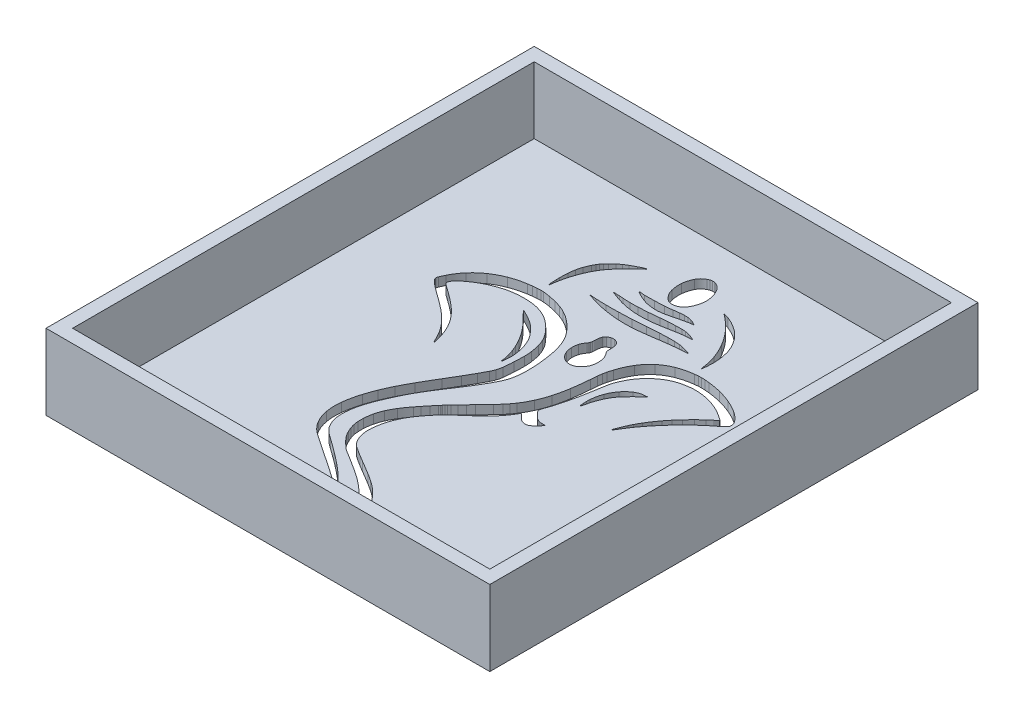
SolidWorks part; units mm, degrees
ref_plane "Front Plane" through (0, 0, 0) normal (0, 0, 1) x (1, 0, 0)
ref_plane "Top Plane" through (0, 0, 0) normal (0, 1, 0) x (1, 0, 0)
ref_plane "Right Plane" through (0, 0, 0) normal (1, 0, 0) x (0, 0, -1)
sketch "Sketch1" plane through (0, 0, 0) normal (0, 1, 0) x (1, 0, 0)
  line L1 (-50, 55) -> (50, 55)
  line L2 (-50, 55) -> (-50, -55)
  line L3 (-50, -55) -> (50, -55)
  line L4 (50, 55) -> (50, -55)
  line L5 (-50, 55) -> (50, -55) construction
  line L6 (-50, -55) -> (50, 55) construction
  point P0 (0, 0)
  dimension "D1" = 110
  dimension "D2" = 100
extrude "Boss-Extrude1" add sketch "Sketch1" along normal blind 2
sketch "Sketch2" plane through (0, 2, 0) normal (0, 1, 0) x (1, 0, 0)
  line L11 (50, 55) -> (-50, 55) construction
  line L12 (50, -55) -> (50, 55) construction
  line L13 (-50, -55) -> (50, -55) construction
  line L14 (-50, 55) -> (-50, -55) construction
  line L15 (47, 52) -> (-47, 52)
  line L16 (47, -52) -> (47, 52)
  line L17 (-47, -52) -> (47, -52)
  line L18 (-47, 52) -> (-47, -52)
  line L19 (47, 52) -> (-47, 52)
  line L20 (47, -52) -> (47, 52)
  line L21 (-47, -52) -> (47, -52)
  line L22 (-47, 52) -> (-47, -52)
  line L23 (50, 55) -> (-50, 55)
  line L24 (50, -55) -> (50, 55)
  line L25 (-50, -55) -> (50, -55)
  line L26 (-50, 55) -> (-50, -55)
  dimension "D1" = 3
extrude "Boss-Extrude2" add sketch "Sketch2" along normal blind 15
sketch "Sketch4" plane through (0, 0, 0) normal (0, -1, 0) x (1, 0, 0)
  line L0 (9.4741, -38.4821) -> (9.1865, -38.7106)
  line L1 (8.9359, -38.9105) -> (8.721, -39.0824)
  line L2 (6.9419, -33.8902) -> (7.3474, -33.6335)
  line L3 (7.3474, -33.6335) -> (6.6825, -33.5473)
  line L4 (6.9435, -30.2628) -> (6.2805, -30.1435)
  line L5 (6.2805, -30.1435) -> (5.4513, -29.9942)
  line L6 (5.4513, -29.9942) -> (4.5988, -29.8406)
  line L7 (4.5988, -29.8406) -> (3.8574, -29.707)
  line L8 (-8.9808, -27.3617) -> (-10.277, -27.7919)
  line L9 (-10.277, -27.7919) -> (-8.7339, -27.7062)
  line L10 (9.5003, 2.7221) -> (10.1461, 2.7221)
  line L11 (10.1461, 2.7221) -> (9.9335, 3.0852)
  line L12 (-5.4816, 10.5411) -> (-5.2835, 10.3261)
  line L13 (15.4299, -14.3103) -> (16.14, -14.3779)
  line L14 (16.14, -14.3779) -> (14.7062, -12.9744)
  arc A0 (1.7289, -44.1609) -> (2.2683, -43.8703) centre (0.2772, -40.8206) ccw
  arc A1 (2.2683, -43.8703) -> (2.7079, -43.5117) centre (0.8011, -41.623) ccw
  arc A2 (2.7079, -43.5117) -> (3.0821, -43.05) centre (0.582, -41.4061) ccw
  arc A3 (3.0821, -43.05) -> (3.426, -42.4476) centre (-1.521, -40.0232) ccw
  arc A4 (3.426, -42.4476) -> (3.7762, -41.5765) centre (-2.3242, -39.6296) ccw
  arc A5 (3.7762, -41.5765) -> (3.9968, -40.6604) centre (-2.4134, -39.6011) ccw
  arc A6 (3.9968, -40.6604) -> (4.0782, -39.7497) centre (-2.0474, -39.6616) ccw
  arc A7 (4.0782, -39.7497) -> (4.013, -38.895) centre (-0.6645, -39.6815) ccw
  arc A8 (4.013, -38.895) -> (3.5881, -37.3522) centre (-3.726, -40.1963) ccw
  arc A9 (3.5881, -37.3522) -> (2.895, -36.1872) centre (-0.2386, -38.8402) ccw
  arc A10 (2.895, -36.1872) -> (1.9771, -35.4661) centre (0.6794, -38.063) ccw
  arc A11 (1.9771, -35.4661) -> (0.8935, -35.2105) centre (0.8935, -37.6345) ccw
  arc A12 (0.8935, -35.2105) -> (0.3834, -35.2531) centre (0.8935, -38.2859) ccw
  arc A13 (0.3834, -35.2531) -> (-0.0297, -35.3822) centre (0.6475, -36.8233) ccw
  arc A14 (-0.0297, -35.3822) -> (-0.4186, -35.6279) centre (0.7597, -37.0622) ccw
  arc A15 (-0.4186, -35.6279) -> (-0.8579, -36.0335) centre (2.8687, -39.6292) ccw
  arc A16 (-0.8579, -36.0335) -> (-1.9288, -37.9241) centre (2.2762, -39.0575) ccw
  arc A17 (-1.9288, -37.9241) -> (-2.1348, -40.3651) centre (4.7098, -39.7134) ccw
  arc A18 (-2.1348, -40.3651) -> (-1.4793, -42.6246) centre (4.1492, -39.7668) ccw
  arc A19 (-1.4793, -42.6246) -> (-0.0989, -44.0059) centre (1.3285, -41.199) ccw
  arc A20 (-0.0989, -44.0059) -> (0.4205, -44.2275) centre (1.8111, -40.2501) ccw
  arc A21 (0.4205, -44.2275) -> (0.8661, -44.3227) centre (1.0195, -42.5143) ccw
  arc A22 (0.8661, -44.3227) -> (1.2871, -44.2992) centre (0.9933, -42.8237) ccw
  arc A23 (1.2871, -44.2992) -> (1.7289, -44.1609) centre (0.8626, -42.1677) ccw
  arc A24 (-8.8634, -39.1915) -> (-8.8888, -39.1359) centre (-8.949, -39.1971) ccw
  arc A25 (-8.8888, -39.1359) -> (-9.0687, -38.963) centre (-16.1756, -46.5363) ccw
  arc A26 (-9.0687, -38.963) -> (-9.2912, -38.763) centre (-13.8128, -44.0184) ccw
  arc A27 (-9.2912, -38.763) -> (-9.554, -38.5435) centre (-17.0369, -47.7657) ccw
  arc A28 (-10.5478, -37.6517) -> (-9.554, -38.5435) centre (-1.0854, -28.1065) ccw
  arc A29 (-11.7644, -36.3903) -> (-10.5478, -37.6517) centre (16.995, -9.8678) ccw
  arc A30 (-12.9131, -35.0877) -> (-11.7644, -36.3903) centre (16.9125, -9.9439) ccw
  arc A31 (-13.6783, -34.0713) -> (-12.9131, -35.0877) centre (-4.0861, -27.6462) ccw
  arc A32 (-14.6996, -32.3138) -> (-13.6783, -34.0713) centre (-0.4277, -25.1958) ccw
  arc A33 (-15.5419, -30.3599) -> (-14.6996, -32.3138) centre (2.4192, -23.7759) ccw
  arc A34 (-16.1961, -28.2317) -> (-15.5419, -30.3599) centre (4.1454, -23.1432) ccw
  arc A35 (-16.6545, -25.9522) -> (-16.1961, -28.2317) centre (7.9839, -22.183) ccw
  arc A36 (-16.6545, -25.9522) -> (-16.7671, -25.2277) centre (-171.9124, -49.7034) ccw
  arc A37 (-16.7671, -25.2277) -> (-16.8055, -25.1076) centre (-17.1758, -25.2922) ccw
  arc A38 (-16.8055, -25.1076) -> (-16.8415, -25.1126) centre (-16.8227, -25.1161) ccw
  arc A39 (-16.8415, -25.1126) -> (-16.9007, -25.4584) centre (-6.4015, -27.0774) ccw
  arc A40 (-16.9007, -25.4584) -> (-16.9344, -25.7734) centre (-13.5337, -25.9776) ccw
  arc A41 (-16.9344, -25.7734) -> (-16.9632, -26.3403) centre (13.8166, -27.6197) ccw
  arc A42 (-16.9632, -26.3403) -> (-16.9842, -27.0016) centre (16.9845, -27.7514) ccw
  arc A43 (-16.9842, -27.0016) -> (-16.9931, -27.6804) centre (20.6271, -27.8317) ccw
  arc A44 (-16.9931, -27.6804) -> (-16.937, -29.5435) centre (10.3356, -27.7904) ccw
  arc A45 (-16.937, -29.5435) -> (-16.7444, -31.0353) centre (-5.2433, -28.7918) ccw
  arc A46 (-16.7444, -31.0353) -> (-16.3833, -32.3655) centre (-7.3894, -29.2104) ccw
  arc A47 (-16.3833, -32.3655) -> (-15.8145, -33.7223) centre (-4.7282, -28.2768) ccw
  arc A48 (-15.8145, -33.7223) -> (-15.4698, -34.3737) centre (-4.8328, -28.3282) ccw
  arc A49 (-15.4698, -34.3737) -> (-15.1491, -34.8688) centre (-11.0507, -31.8621) ccw
  arc A50 (-15.1491, -34.8688) -> (-14.7571, -35.3469) centre (-10.5158, -31.4697) ccw
  arc A51 (-14.7571, -35.3469) -> (-14.179, -35.9517) centre (-0.889, -22.6694) ccw
  arc A52 (-14.179, -35.9517) -> (-13.3082, -36.7655) centre (-1.8206, -23.6004) ccw
  arc A53 (-13.3082, -36.7655) -> (-12.5035, -37.3945) centre (-7.0853, -29.634) ccw
  arc A54 (-12.5035, -37.3945) -> (-11.5831, -37.972) centre (-6.1763, -28.3319) ccw
  arc A55 (-11.5831, -37.972) -> (-10.3387, -38.6329) centre (3.449, -11.1709) ccw
  arc A56 (-10.3387, -38.6329) -> (-9.4767, -39.0605) centre (34.8818, 51.4367) ccw
  arc A57 (-9.4767, -39.0605) -> (-9.1044, -39.2218) centre (-7.5717, -35.1742) ccw
  arc A58 (-9.1044, -39.2218) -> (-8.9254, -39.2564) centre (-8.9146, -38.7204) ccw
  arc A59 (-8.9254, -39.2564) -> (-8.8634, -39.1915) centre (-8.9242, -39.1955) ccw
  arc A60 (9.848, -38.862) -> (13.082, -37.0123) centre (5.4219, -27.3712) ccw
  arc A61 (13.082, -37.0123) -> (15.4143, -34.3622) centre (6.8703, -29.1942) ccw
  arc A62 (15.4143, -34.3622) -> (16.7088, -31.0217) centre (6.576, -29.0161) ccw
  arc A63 (16.7088, -31.0217) -> (16.9231, -27.165) centre (3.1204, -28.3321) ccw
  arc A64 (16.9231, -27.165) -> (16.8787, -26.6799) centre (-17.9614, -30.1147) ccw
  arc A65 (16.8787, -26.6799) -> (16.833, -26.2628) centre (-2.3442, -28.575) ccw
  arc A66 (16.833, -26.2628) -> (16.7885, -25.9044) centre (-32.6996, -32.235) ccw
  arc A67 (16.7885, -25.9044) -> (16.7655, -25.8575) centre (16.7084, -25.9146) ccw
  arc A68 (16.7655, -25.8575) -> (16.7419, -25.8636) centre (16.7555, -25.8675) ccw
  arc A69 (16.7419, -25.8636) -> (16.7072, -25.9968) centre (19.122, -26.5541) ccw
  arc A70 (16.7072, -25.9968) -> (16.6717, -26.1781) centre (19.405, -26.6194) ccw
  arc A71 (16.6717, -26.1781) -> (16.6394, -26.4038) centre (22.9506, -27.1918) ccw
  arc A72 (15.8488, -29.6954) -> (16.6394, -26.4038) centre (1.5473, -24.5193) ccw
  arc A73 (14.3174, -32.9369) -> (15.8488, -29.6954) centre (-2.0917, -23.2023) ccw
  arc A74 (12.1505, -35.9293) -> (14.3174, -32.9369) centre (-3.1083, -22.5992) ccw
  arc A75 (9.4741, -38.4821) -> (12.1505, -35.9293) centre (-3.1744, -22.5415) ccw
  arc A76 (9.1865, -38.7106) -> (8.9359, -38.9105) centre (101.7829, -155.0642) ccw
  arc A77 (8.721, -39.0824) -> (8.682, -39.1152) centre (9.3758, -39.9002) ccw
  arc A78 (8.682, -39.1152) -> (8.7039, -39.1691) centre (8.7024, -39.1383) ccw
  arc A79 (8.7039, -39.1691) -> (8.9648, -39.1344) centre (8.6219, -37.5561) ccw
  arc A80 (8.9648, -39.1344) -> (9.3872, -39.0226) centre (7.9271, -34.3573) ccw
  arc A81 (9.3872, -39.0226) -> (9.848, -38.862) centre (7.1222, -31.7854) ccw
  arc A82 (5.9684, -34.3001) -> (6.2155, -34.2227) centre (5.1256, -31.1731) ccw
  arc A83 (6.2155, -34.2227) -> (6.4887, -34.1165) centre (4.4294, -29.2249) ccw
  arc A84 (6.4887, -34.1165) -> (6.746, -33.9996) centre (4.5224, -29.4459) ccw
  arc A85 (6.746, -33.9996) -> (6.9419, -33.8902) centre (5.8522, -32.1692) ccw
  arc A86 (6.3101, -33.4852) -> (6.6825, -33.5473) centre (7.3544, -28.3658) ccw
  arc A87 (5.6509, -33.3458) -> (6.3101, -33.4852) centre (15.6368, 12.2372) ccw
  arc A88 (4.8855, -33.172) -> (5.6509, -33.3458) centre (16.6627, 16.9199) ccw
  arc A89 (4.1042, -32.9825) -> (4.8855, -33.172) centre (17.8547, 21.9895) ccw
  arc A90 (4.1042, -32.9825) -> (2.022, -32.495) centre (-13.0438, -101.5374) ccw
  arc A91 (2.022, -32.495) -> (0.727, -32.2932) centre (-0.2959, -43.1174) ccw
  arc A92 (0.727, -32.2932) -> (-0.3656, -32.281) centre (0.1071, -38.8526) ccw
  arc A93 (-0.3656, -32.281) -> (-1.6506, -32.4386) centre (0.559, -45.1332) ccw
  arc A94 (-1.6506, -32.4386) -> (-2.2264, -32.5609) centre (-0.2837, -40.2915) ccw
  arc A95 (-2.2264, -32.5609) -> (-2.7823, -32.7238) centre (-0.4051, -39.8086) ccw
  arc A96 (-2.7823, -32.7238) -> (-3.3581, -32.9404) centre (-0.0679, -40.8136) ccw
  arc A97 (-3.3581, -32.9404) -> (-3.9952, -33.2253) centre (2.0769, -45.946) ccw
  arc A98 (-3.9952, -33.2253) -> (-4.8506, -33.6492) centre (9.9822, -62.5071) ccw
  arc A99 (-4.8506, -33.6492) -> (-5.2638, -33.9117) centre (-3.6214, -36.0407) ccw
  arc A100 (-5.2638, -33.9117) -> (-5.2442, -34.0032) centre (-5.2322, -33.9528) ccw
  arc A101 (-5.2442, -34.0032) -> (-5.0059, -34.005) centre (-5.121, -33.4882) ccw
  arc A102 (-3.9964, -33.8932) -> (-5.0059, -34.005) centre (-3.9896, -38.568) ccw
  arc A103 (-1.8469, -33.9212) -> (-3.9964, -33.8932) centre (-3.8884, -108.1364) ccw
  arc A104 (0.3772, -34.0227) -> (-1.8469, -33.9212) centre (-3.5398, -95.4608) ccw
  arc A105 (2.0356, -34.1987) -> (0.3772, -34.0227) centre (-0.8834, -53.7959) ccw
  arc A106 (2.0356, -34.1987) -> (3.4065, -34.377) centre (7.5311, 2.6958) ccw
  arc A107 (3.4065, -34.377) -> (4.4449, -34.4481) centre (4.7602, -22.2097) ccw
  arc A108 (4.4449, -34.4481) -> (5.2713, -34.4231) centre (4.6353, -27.0575) ccw
  arc A109 (5.2713, -34.4231) -> (5.9684, -34.3001) centre (4.927, -30.4363) ccw
  arc A110 (7.7458, -31.3869) -> (8.3805, -31.2591) centre (6.9373, -25.7293) ccw
  arc A111 (8.3805, -31.2591) -> (9.1091, -31.0413) centre (5.6474, -20.7873) ccw
  arc A112 (9.1091, -31.0413) -> (9.7774, -30.798) centre (4.2967, -16.7863) ccw
  arc A113 (9.7774, -30.798) -> (9.9728, -30.6351) centre (9.631, -30.4238) ccw
  arc A114 (9.9728, -30.6351) -> (9.9546, -30.5881) centre (9.9459, -30.6185) ccw
  arc A115 (9.9546, -30.5881) -> (9.7875, -30.5519) centre (9.5868, -31.8797) ccw
  arc A116 (9.7875, -30.5519) -> (9.5351, -30.5268) centre (9.4172, -33.0016) ccw
  arc A117 (9.5351, -30.5268) -> (9.2036, -30.5188) centre (9.1967, -37.6289) ccw
  arc A118 (8.7838, -30.5012) -> (9.2036, -30.5188) centre (9.2086, -25.3804) ccw
  arc A119 (8.193, -30.4432) -> (8.7838, -30.5012) centre (10.4182, -10.7998) ccw
  arc A120 (7.5486, -30.3605) -> (8.193, -30.4432) centre (10.6543, -8.7156) ccw
  arc A121 (6.9435, -30.2628) -> (7.5486, -30.3605) centre (10.0106, -13.2016) ccw
  arc A122 (3.8574, -29.707) -> (1.5206, -29.392) centre (-0.8517, -55.8158) ccw
  arc A123 (1.5206, -29.392) -> (-0.7104, -29.309) centre (-0.3872, -50.6425) ccw
  arc A124 (-0.7104, -29.309) -> (-2.833, -29.4582) centre (-0.4175, -48.6478) ccw
  arc A125 (-2.833, -29.4582) -> (-4.8454, -29.8388) centre (-0.759, -45.935) ccw
  arc A126 (-4.8454, -29.8388) -> (-5.7714, -30.1044) centre (-0.9878, -45.0338) ccw
  arc A127 (-5.7714, -30.1044) -> (-6.8606, -30.4753) centre (3.9075, -60.3116) ccw
  arc A128 (-6.8606, -30.4753) -> (-7.9412, -30.8717) centre (30.6515, -134.4139) ccw
  arc A129 (-7.9412, -30.8717) -> (-7.9611, -30.9632) centre (-7.9217, -30.9239) ccw
  arc A130 (-7.9611, -30.9632) -> (-7.9148, -30.9813) centre (-7.9174, -30.9195) ccw
  arc A131 (-7.9148, -30.9813) -> (-7.3393, -30.9567) centre (-15.1158, 144.2638) ccw
  arc A132 (-7.3393, -30.9567) -> (-6.6831, -30.9224) centre (-9.1934, 10.8192) ccw
  arc A133 (-6.6831, -30.9224) -> (-5.9132, -30.8724) centre (-11.4323, 48.0485) ccw
  arc A134 (-4.2512, -30.8085) -> (-5.9132, -30.8724) centre (-4.0658, -57.2897) ccw
  arc A135 (-2.4196, -30.8388) -> (-4.2512, -30.8085) centre (-3.9786, -69.7316) ccw
  arc A136 (-0.3246, -30.9653) -> (-2.4196, -30.8388) centre (-4.4948, -82.6096) ccw
  arc A137 (2.1442, -31.1953) -> (-0.3246, -30.9653) centre (-8.411, -131.1124) ccw
  arc A138 (2.1442, -31.1953) -> (3.8141, -31.3429) centre (7.2857, 17.4746) ccw
  arc A139 (3.8141, -31.3429) -> (5.4485, -31.4289) centre (6.9676, 13.0025) ccw
  arc A140 (5.4485, -31.4289) -> (6.8617, -31.451) centre (6.7518, 6.6899) ccw
  arc A141 (6.8617, -31.451) -> (7.7458, -31.3869) centre (6.8433, -25.0717) ccw
  arc A142 (9.5755, -28.1673) -> (10.3126, -28.0454) centre (8.6783, -20.4488) ccw
  arc A143 (10.3126, -28.0454) -> (11.1761, -27.8336) centre (7.0555, -12.9056) ccw
  arc A144 (11.1761, -27.8336) -> (11.9918, -27.5945) centre (4.0013, -1.8408) ccw
  arc A145 (11.9918, -27.5945) -> (12.1808, -27.4481) centre (11.8908, -27.2689) ccw
  arc A146 (12.1808, -27.4481) -> (12.16, -27.4039) centre (12.156, -27.4328) ccw
  arc A147 (12.16, -27.4039) -> (11.7653, -27.3539) centre (9.8522, -44.0498) ccw
  arc A148 (11.7653, -27.3539) -> (11.2729, -27.3088) centre (10.5306, -38.1294) ccw
  arc A149 (11.2729, -27.3088) -> (10.6749, -27.2756) centre (9.6865, -50.4337) ccw
  arc A150 (9.8793, -27.2206) -> (10.6749, -27.2756) centre (11.3188, -12.1881) ccw
  arc A151 (8.7312, -27.1001) -> (9.8793, -27.2206) centre (15.9427, 36.1008) ccw
  arc A152 (7.4667, -26.9443) -> (8.7312, -27.1001) centre (16.7469, 43.1483) ccw
  arc A153 (6.2645, -26.7723) -> (7.4667, -26.9443) centre (15.129, 30.9278) ccw
  arc A154 (6.2645, -26.7723) -> (4.0099, -26.446) centre (-13.6127, -156.1553) ccw
  arc A155 (4.0099, -26.446) -> (2.2213, -26.2346) centre (-2.9574, -77.727) ccw
  arc A156 (2.2213, -26.2346) -> (0.7169, -26.1159) centre (-1.2971, -61.2181) ccw
  arc A157 (0.7169, -26.1159) -> (-0.6483, -26.0771) centre (-0.6362, -49.7004) ccw
  arc A158 (-0.6483, -26.0771) -> (-2.7871, -26.1623) centre (-0.6344, -53.3099) ccw
  arc A159 (-2.7871, -26.1623) -> (-4.9581, -26.4154) centre (-0.4465, -55.6793) ccw
  arc A160 (-4.9581, -26.4154) -> (-7.0576, -26.8205) centre (-0.6287, -54.4979) ccw
  arc A161 (-7.0576, -26.8205) -> (-8.9808, -27.3617) centre (-2.1525, -47.9377) ccw
  arc A162 (-6.4415, -27.6371) -> (-8.7339, -27.7062) centre (-6.2206, -72.998) ccw
  arc A163 (-3.697, -27.6644) -> (-6.4415, -27.6371) centre (-5.9909, -120.1405) ccw
  arc A164 (-0.6985, -27.7805) -> (-3.697, -27.6644) centre (-6.3768, -135.6995) ccw
  arc A165 (2.376, -27.9818) -> (-0.6985, -27.7805) centre (-7.0108, -147.752) ccw
  arc A166 (2.376, -27.9818) -> (5.0813, -28.1759) centre (18.4307, 176.8643) ccw
  arc A167 (5.0813, -28.1759) -> (6.9381, -28.2602) centre (8.1577, 19.0772) ccw
  arc A168 (6.9381, -28.2602) -> (8.3509, -28.2569) centre (7.586, -3.1142) ccw
  arc A169 (8.3509, -28.2569) -> (9.5755, -28.1673) centre (7.9131, -13.8648) ccw
  arc A170 (20.2754, -24.0838) -> (23.2076, -23.5597) centre (18.2492, -4.2832) ccw
  arc A171 (23.2076, -23.5597) -> (26.0693, -22.5994) centre (17.9798, -3.2358) ccw
  arc A172 (26.0693, -22.5994) -> (28.5596, -21.3284) centre (18.9906, -5.6552) ccw
  arc A173 (28.5596, -21.3284) -> (30.359, -19.8712) centre (23.9955, -13.8529) ccw
  arc A174 (30.359, -19.8712) -> (30.8345, -19.2937) centre (26.3995, -16.1264) ccw
  arc A175 (30.8345, -19.2937) -> (31.1224, -18.7587) centre (28.8746, -17.894) ccw
  arc A176 (31.1224, -18.7587) -> (31.2247, -18.2684) centre (29.6697, -18.1999) ccw
  arc A177 (31.2247, -18.2684) -> (31.1465, -17.8241) centre (30.1846, -18.2226) ccw
  arc A178 (31.1465, -17.8241) -> (31.0173, -17.6216) centre (30.5091, -18.0881) ccw
  arc A179 (31.0173, -17.6216) -> (30.7103, -17.3089) centre (26.1978, -22.046) ccw
  arc A180 (30.7103, -17.3089) -> (30.2998, -16.9424) centre (24.8365, -23.4751) ccw
  arc A181 (30.2998, -16.9424) -> (29.8014, -16.5429) centre (20.4203, -28.7559) ccw
  arc A182 (26.8504, -14.0375) -> (29.8014, -16.5429) centre (53.9177, 14.8536) ccw
  arc A183 (23.9603, -11.1008) -> (26.8504, -14.0375) centre (61.562, 23.0131) ccw
  arc A184 (21.3714, -7.9997) -> (23.9603, -11.1008) centre (60.2993, 21.8674) ccw
  arc A185 (19.3306, -5.0016) -> (21.3714, -7.9997) centre (46.7179, 11.4471) ccw
  arc A186 (19.3306, -5.0016) -> (19.0299, -4.5113) centre (-7.165, -20.9147) ccw
  arc A187 (19.0299, -4.5113) -> (18.7773, -4.1233) centre (7.9218, -11.4673) ccw
  arc A188 (18.7773, -4.1233) -> (18.5765, -3.8342) centre (6.8673, -12.1807) ccw
  arc A189 (18.5765, -3.8342) -> (18.5472, -3.8435) centre (18.5634, -3.8435) ccw
  arc A190 (18.5472, -3.8435) -> (18.6129, -4.2024) centre (19.5594, -3.8435) ccw
  arc A191 (18.6129, -4.2024) -> (19.0664, -5.3692) centre (89.1305, 22.5324) ccw
  arc A192 (19.0664, -5.3692) -> (19.5558, -6.545) centre (57.4435, 9.9137) ccw
  arc A193 (19.5558, -6.545) -> (19.98, -7.4415) centre (33.6982, -0.4014) ccw
  arc A194 (19.98, -7.4415) -> (20.6727, -8.6849) centre (38.5299, 2.0782) ccw
  arc A195 (20.6727, -8.6849) -> (21.5087, -9.9927) centre (45.8982, 6.5194) ccw
  arc A196 (21.5087, -9.9927) -> (22.4461, -11.304) centre (47.6721, 7.7204) ccw
  arc A197 (22.4461, -11.304) -> (23.4443, -12.5585) centre (47.134, 7.3146) ccw
  arc A198 (23.4443, -12.5585) -> (24.5693, -13.8284) centre (47.5735, 7.6833) ccw
  arc A199 (24.5693, -13.8284) -> (25.9202, -15.2218) centre (63.8663, 22.919) ccw
  arc A200 (25.9202, -15.2218) -> (27.2377, -16.4867) centre (62.1223, 21.1661) ccw
  arc A201 (27.2377, -16.4867) -> (28.2153, -17.3052) centre (35.8586, -7.1817) ccw
  arc A202 (28.4841, -17.5112) -> (28.2153, -17.3052) centre (14.2536, -35.7974) ccw
  arc A203 (28.7105, -17.6917) -> (28.4841, -17.5112) centre (20.8535, -27.3165) ccw
  arc A204 (28.9038, -17.8505) -> (28.7105, -17.6917) centre (5.3637, -46.2913) ccw
  arc A205 (28.9165, -17.8775) -> (28.9038, -17.8505) centre (28.8814, -17.8775) ccw
  arc A206 (28.8551, -17.9948) -> (28.9165, -17.8775) centre (28.7737, -17.8775) ccw
  arc A207 (28.1151, -18.5022) -> (28.8551, -17.9948) centre (-15.2998, 45.614) ccw
  arc A208 (27.3544, -18.9971) -> (28.1151, -18.5022) centre (14.3074, 1.8893) ccw
  arc A209 (26.6774, -19.3937) -> (27.3544, -18.9971) centre (20.0445, -7.295) ccw
  arc A210 (24.8431, -20.228) -> (26.6774, -19.3937) centre (20.178, -7.5386) ccw
  arc A211 (22.8768, -20.7958) -> (24.8431, -20.228) centre (19.881, -6.7308) ccw
  arc A212 (20.9091, -21.0664) -> (22.8768, -20.7958) centre (20.0479, -7.5144) ccw
  arc A213 (19.0717, -21.0136) -> (20.9091, -21.0664) centre (20.2756, -11.0981) ccw
  arc A214 (17.0975, -20.6301) -> (19.0717, -21.0136) centre (20.779, -6.9525) ccw
  arc A215 (15.3863, -19.9909) -> (17.0975, -20.6301) centre (19.6115, -11.2897) ccw
  arc A216 (13.8574, -19.0558) -> (15.3863, -19.9909) centre (19.4345, -11.6544) ccw
  arc A217 (12.4287, -17.7879) -> (13.8574, -19.0558) centre (21.0381, -9.5261) ccw
  arc A218 (11.7488, -17.0416) -> (12.4287, -17.7879) centre (26.5014, -4.2835) ccw
  arc A219 (11.2425, -16.3962) -> (11.7488, -17.0416) centre (18.2405, -11.4276) ccw
  arc A220 (10.8043, -15.7111) -> (11.2425, -16.3962) centre (18.093, -11.5323) ccw
  arc A221 (10.3373, -14.8422) -> (10.8043, -15.7111) centre (26.4542, -6.7386) ccw
  arc A222 (9.8708, -13.8259) -> (10.3373, -14.8422) centre (24.3777, -7.7826) ccw
  arc A223 (9.5611, -12.9373) -> (9.8708, -13.8259) centre (17.1927, -10.7758) ccw
  arc A224 (9.3137, -11.8784) -> (9.5611, -12.9373) centre (20.8222, -9.7478) ccw
  arc A225 (9.0334, -10.2387) -> (9.3137, -11.8784) centre (68.6584, -0.8914) ccw
  arc A226 (9.0334, -10.2387) -> (8.5363, -7.3861) centre (-74.9732, -23.4083) ccw
  arc A227 (8.5363, -7.3861) -> (7.9718, -4.7446) centre (-54.7138, -19.5213) ccw
  arc A228 (7.9718, -4.7446) -> (7.3674, -2.4214) centre (-42.7315, -16.6967) ccw
  arc A229 (7.3674, -2.4214) -> (6.7491, -0.5481) centre (-15.6599, -8.9829) ccw
  arc A230 (6.635, -0.2121) -> (6.7491, -0.5481) centre (11.8474, 1.3709) ccw
  arc A231 (6.5492, 0.1143) -> (6.635, -0.2121) centre (10.8973, 1.0823) ccw
  arc A232 (6.4977, 0.3932) -> (6.5492, 0.1143) centre (10.3397, 0.9582) ccw
  arc A233 (6.5054, 0.5465) -> (6.4977, 0.3932) centre (6.8878, 0.4506) ccw
  arc A234 (6.6994, 0.9298) -> (6.5054, 0.5465) centre (7.4484, 0.3099) ccw
  arc A235 (7.2526, 1.5497) -> (6.6994, 0.9298) centre (15.2956, -6.1843) ccw
  arc A236 (7.8674, 2.1373) -> (7.2526, 1.5497) centre (14.5213, -5.4397) ccw
  arc A237 (8.3499, 2.4647) -> (7.8674, 2.1373) centre (9.4175, 0.3721) ccw
  arc A238 (8.6057, 2.5737) -> (8.3499, 2.4647) centre (9.265, 0.6709) ccw
  arc A239 (8.8914, 2.6548) -> (8.6057, 2.5737) centre (9.4632, 0.0991) ccw
  arc A240 (9.1939, 2.7052) -> (8.8914, 2.6548) centre (9.4999, -0.065) ccw
  arc A241 (9.5003, 2.7221) -> (9.1939, 2.7052) centre (9.5003, -0.0684) ccw
  arc A242 (9.9335, 3.0852) -> (9.5984, 3.5372) centre (7.6882, 1.7706) ccw
  arc A243 (9.5984, 3.5372) -> (9.0901, 4.0292) centre (4.9019, -0.8061) ccw
  arc A244 (9.0901, 4.0292) -> (8.5523, 4.4465) centre (4.9638, -0.7346) ccw
  arc A245 (8.5523, 4.4465) -> (8.1386, 4.64) centre (7.7754, 3.3249) ccw
  arc A246 (8.1386, 4.64) -> (7.5355, 4.7115) centre (7.6024, 2.6983) ccw
  arc A247 (7.5355, 4.7115) -> (6.9736, 4.5912) centre (7.5895, 3.0873) ccw
  arc A248 (6.9736, 4.5912) -> (6.407, 4.2557) centre (7.8319, 2.4954) ccw
  arc A249 (6.407, 4.2557) -> (5.7839, 3.6757) centre (10.2833, -0.5329) ccw
  arc A250 (5.5538, 3.4351) -> (5.7839, 3.6757) centre (-5.1, 13.8564) ccw
  arc A251 (5.3545, 3.2389) -> (5.5538, 3.4351) centre (0.22, 8.6525) ccw
  arc A252 (5.1831, 3.0786) -> (5.3545, 3.2389) centre (-6.1603, 15.3797) ccw
  arc A253 (5.1558, 3.0799) -> (5.1831, 3.0786) centre (5.1701, 3.0926) ccw
  arc A254 (5.1326, 3.1111) -> (5.1558, 3.0799) centre (5.328, 3.2324) ccw
  arc A255 (5.0115, 3.3069) -> (5.1326, 3.1111) centre (84.3921, 52.2833) ccw
  arc A256 (4.8719, 3.5348) -> (5.0115, 3.3069) centre (38.6783, 24.0787) ccw
  arc A257 (4.7129, 3.7978) -> (4.8719, 3.5348) centre (63.8171, 39.3554) ccw
  arc A258 (4.7129, 3.7978) -> (3.7367, 5.2472) centre (-9.936, -5.0151) ccw
  arc A259 (3.7367, 5.2472) -> (2.6029, 6.6137) centre (-10.8357, -5.6904) ccw
  arc A260 (2.6029, 6.6137) -> (1.1222, 8.1102) centre (-17.4461, -11.7426) ccw
  arc A261 (1.1222, 8.1102) -> (-0.957, 9.9905) centre (-56.0153, -52.9799) ccw
  arc A262 (-2.5152, 11.3903) -> (-0.957, 9.9905) centre (50.3771, 68.7013) ccw
  arc A263 (-3.6187, 12.477) -> (-2.5152, 11.3903) centre (13.6813, 28.9399) ccw
  arc A264 (-4.5739, 13.5567) -> (-3.6187, 12.477) centre (10.767, 26.1667) ccw
  arc A265 (-5.6394, 14.911) -> (-4.5739, 13.5567) centre (26.5651, 39.1525) ccw
  arc A266 (-6.894, 16.8112) -> (-5.6394, 14.911) centre (9.1174, 26.019) ccw
  arc A267 (-7.8399, 18.7652) -> (-6.894, 16.8112) centre (6.3489, 24.427) ccw
  arc A268 (-8.472, 20.7667) -> (-7.8399, 18.7652) centre (5.3856, 24.0426) ccw
  arc A269 (-8.7906, 22.8082) -> (-8.472, 20.7667) centre (4.548, 23.8446) ccw
  arc A270 (-8.7742, 24.2853) -> (-8.7906, 22.8082) centre (-0.4765, 23.4542) ccw
  arc A271 (-8.4923, 25.6733) -> (-8.7742, 24.2853) centre (-1.751, 23.5818) ccw
  arc A272 (-7.968, 26.8829) -> (-8.4923, 25.6733) centre (-2.6625, 23.8646) ccw
  arc A273 (-7.2323, 27.831) -> (-7.968, 26.8829) centre (-4.3008, 24.7966) ccw
  arc A274 (-6.8599, 28.1306) -> (-7.2323, 27.831) centre (-5.3989, 25.9332) ccw
  arc A275 (-5.8803, 28.7697) -> (-6.8599, 28.1306) centre (30.669, -28.3127) ccw
  arc A276 (-4.6841, 29.5175) -> (-5.8803, 28.7697) centre (29.2209, -26.0512) ccw
  arc A277 (-3.3485, 30.3177) -> (-4.6841, 29.5175) centre (45.576, -52.8564) ccw
  arc A278 (-3.3485, 30.3177) -> (-0.4275, 32.0646) centre (-121.8652, 231.8023) ccw
  arc A279 (-0.4275, 32.0646) -> (1.3976, 33.2408) centre (-21.9741, 67.5039) ccw
  arc A280 (1.3976, 33.2408) -> (2.7018, 34.2088) centre (-10.0859, 50.0756) ccw
  arc A281 (2.7018, 34.2088) -> (3.8161, 35.2048) centre (-6.4791, 45.6004) ccw
  arc A282 (3.8161, 35.2048) -> (6.4081, 38.4822) centre (-8.3547, 47.4942) ccw
  arc A283 (6.4081, 38.4822) -> (7.513, 41.7059) centre (-0.3197, 42.5892) ccw
  arc A284 (7.513, 41.7059) -> (7.0758, 44.7332) centre (1.505, 42.3834) ccw
  arc A285 (7.0758, 44.7332) -> (5.1974, 47.4541) centre (-0.4045, 41.578) ccw
  arc A286 (5.1974, 47.4541) -> (4.6391, 47.9253) centre (1.0251, 43.0776) ccw
  arc A287 (4.6391, 47.9253) -> (3.8631, 48.4706) centre (-5.4499, 34.3923) ccw
  arc A288 (3.8631, 48.4706) -> (3.0646, 48.9673) centre (-5.4116, 34.4502) ccw
  arc A289 (3.0646, 48.9673) -> (2.4392, 49.2786) centre (0.4171, 44.4329) ccw
  arc A290 (2.4392, 49.2786) -> (1.9732, 49.4507) centre (0.1448, 43.7805) ccw
  arc A291 (1.9732, 49.4507) -> (1.498, 49.5818) centre (0.2, 43.9516) ccw
  arc A292 (1.498, 49.5818) -> (1.0869, 49.6642) centre (-0.1434, 42.4622) ccw
  arc A293 (1.0869, 49.6642) -> (1.0181, 49.6062) centre (1.077, 49.6062) ccw
  arc A294 (1.0181, 49.6062) -> (1.0417, 49.5543) centre (1.0872, 49.6062) ccw
  arc A295 (1.0417, 49.5543) -> (1.2521, 49.3733) centre (10.3036, 60.1123) ccw
  arc A296 (1.2521, 49.3733) -> (1.5094, 49.1653) centre (6.5028, 55.6029) ccw
  arc A297 (1.5094, 49.1653) -> (1.8147, 48.9349) centre (10.3973, 60.6238) ccw
  arc A298 (2.9153, 47.9926) -> (1.8147, 48.9349) centre (-3.9324, 41.1077) ccw
  arc A299 (3.9065, 46.8648) -> (2.9153, 47.9926) centre (-4.9768, 40.0576) ccw
  arc A300 (4.6956, 45.6713) -> (3.9065, 46.8648) centre (-4.2532, 40.6121) ccw
  arc A301 (5.1868, 44.5343) -> (4.6956, 45.6713) centre (-0.3641, 42.8108) ccw
  arc A302 (5.36, 43.6793) -> (5.1868, 44.5343) centre (1.0615, 43.2535) ccw
  arc A303 (5.4026, 42.6281) -> (5.36, 43.6793) centre (-3.633, 42.7884) ccw
  arc A304 (5.3234, 41.5898) -> (5.4026, 42.6281) centre (-3.5208, 42.7864) ccw
  arc A305 (5.1202, 40.7777) -> (5.3234, 41.5898) centre (1.5721, 42.0973) ccw
  arc A306 (4.2126, 39.054) -> (5.1202, 40.7777) centre (-2.0011, 43.4263) ccw
  arc A307 (2.709, 37.2128) -> (4.2126, 39.054) centre (-9.3652, 48.6081) ccw
  arc A308 (0.7048, 35.3405) -> (2.709, 37.2128) centre (-13.1496, 52.1797) ccw
  arc A309 (-1.7295, 33.5199) -> (0.7048, 35.3405) centre (-20.154, 60.6932) ccw
  arc A310 (-2.7772, 32.8291) -> (-1.7295, 33.5199) centre (-29.1209, 73.9182) ccw
  arc A311 (-4.4547, 31.7618) -> (-2.7772, 32.8291) centre (-157.1404, 273.5943) ccw
  arc A312 (-6.1369, 30.7078) -> (-4.4547, 31.7618) centre (-158.1392, 275.1761) ccw
  arc A313 (-7.1909, 30.0718) -> (-6.1369, 30.7078) centre (-30.4783, 69.8565) ccw
  arc A314 (-7.1909, 30.0718) -> (-7.4559, 29.8865) centre (-6.1772, 28.34) ccw
  arc A315 (-7.4559, 29.8865) -> (-7.9029, 29.5051) centre (4.6565, 15.2379) ccw
  arc A316 (-7.9029, 29.5051) -> (-8.4117, 29.0421) centre (5.971, 13.7447) ccw
  arc A317 (-8.4117, 29.0421) -> (-8.9215, 28.5483) centre (7.8804, 11.7139) ccw
  arc A318 (-8.9215, 28.5483) -> (-9.6078, 27.8394) centre (11.3883, 8.1992) ccw
  arc A319 (-9.6078, 27.8394) -> (-10.0414, 27.325) centre (-4.8555, 23.3939) ccw
  arc A320 (-10.0414, 27.325) -> (-10.3816, 26.8148) centre (-6.0027, 24.2636) ccw
  arc A321 (-10.3816, 26.8148) -> (-10.7462, 26.1412) centre (0.148, 20.6801) ccw
  arc A322 (-10.7462, 26.1412) -> (-11.2317, 25.0357) centre (-0.1237, 20.8162) ccw
  arc A323 (-11.2317, 25.0357) -> (-11.523, 24.0373) centre (-5.0833, 22.7002) ccw
  arc A324 (-11.523, 24.0373) -> (-11.6555, 22.9962) centre (-4.9404, 22.6705) ccw
  arc A325 (-11.6555, 22.9962) -> (-11.6561, 21.7589) centre (1.2271, 22.3714) ccw
  arc A326 (-11.6561, 21.7589) -> (-11.3838, 19.8328) centre (-1.1911, 22.2564) ccw
  arc A327 (-11.3838, 19.8328) -> (-10.7579, 17.9563) centre (-0.4936, 22.4223) ccw
  arc A328 (-10.7579, 17.9563) -> (-9.732, 16.0267) centre (2.0545, 23.531) ccw
  arc A329 (-9.732, 16.0267) -> (-8.2523, 13.9358) centre (12.377, 30.1031) ccw
  arc A330 (-8.2523, 13.9358) -> (-7.506, 12.9946) centre (73.9014, 78.3203) ccw
  arc A331 (-7.506, 12.9946) -> (-6.6122, 11.8888) centre (151.55, 140.6295) ccw
  arc A332 (-6.6122, 11.8888) -> (-5.728, 10.8056) centre (386.8611, 332.1669) ccw
  arc A333 (-5.728, 10.8056) -> (-5.5267, 10.5872) centre (-3.7773, 12.4024) ccw
  arc A334 (-5.4816, 10.5411) -> (-5.5267, 10.5872) centre (-6.2907, 9.7946) ccw
  arc A335 (-5.0515, 10.0731) -> (-5.2835, 10.3261) centre (-84.9105, -62.9269) ccw
  arc A336 (-4.7885, 9.7849) -> (-5.0515, 10.0731) centre (-138.1361, -111.581) ccw
  arc A337 (-4.7885, 9.7849) -> (-4.3894, 9.3539) centre (20.2222, 32.5483) ccw
  arc A338 (-4.3894, 9.3539) -> (-3.5998, 8.5184) centre (297.8584, 294.197) ccw
  arc A339 (-3.5998, 8.5184) -> (-2.6667, 7.5368) centre (316.8271, 312.1724) ccw
  arc A340 (-2.6667, 7.5368) -> (-1.6885, 6.5136) centre (379.0326, 371.4852) ccw
  arc A341 (0.256, 4.47) -> (-1.6885, 6.5136) centre (-275.2406, -255.7228) ccw
  arc A342 (1.3107, 3.3099) -> (0.256, 4.47) centre (-29.7309, -23.8511) ccw
  arc A343 (2.031, 2.4306) -> (1.3107, 3.3099) centre (-11.8596, -8.214) ccw
  arc A344 (2.686, 1.5141) -> (2.031, 2.4306) centre (-11.3701, -7.8388) ccw
  arc A345 (4.0854, -1.0295) -> (2.686, 1.5141) centre (-11.6917, -8.0528) ccw
  arc A346 (5.1256, -3.9071) -> (4.0854, -1.0295) centre (-15.3579, -9.6848) ccw
  arc A347 (5.8574, -7.2932) -> (5.1256, -3.9071) centre (-21.7519, -11.4884) ccw
  arc A348 (6.3246, -11.3858) -> (5.8574, -7.2932) centre (-48.9753, -15.6249) ccw
  arc A349 (6.3246, -11.3858) -> (6.451, -12.8095) centre (65.6191, -6.8405) ccw
  arc A350 (6.451, -12.8095) -> (6.584, -13.7784) centre (20.0162, -11.441) ccw
  arc A351 (6.584, -13.7784) -> (6.7752, -14.6605) centre (17.3841, -11.899) ccw
  arc A352 (6.7752, -14.6605) -> (7.0863, -15.7631) centre (33.9482, -7.5874) ccw
  arc A353 (7.0863, -15.7631) -> (8.5621, -19.0734) centre (21.1134, -11.4938) ccw
  arc A354 (8.5621, -19.0734) -> (10.7012, -21.5735) centre (17.1633, -13.8792) ccw
  arc A355 (10.7012, -21.5735) -> (13.5233, -23.2391) centre (17.1013, -13.953) ccw
  arc A356 (13.5233, -23.2391) -> (17.0071, -24.095) centre (18.6205, -10.0102) ccw
  arc A357 (17.0071, -24.095) -> (17.8657, -24.1762) centre (19.4888, -2.4306) ccw
  arc A358 (17.8657, -24.1762) -> (18.5506, -24.2005) centre (18.5204, -15.4057) ccw
  arc A359 (18.5506, -24.2005) -> (19.2747, -24.1723) centre (18.5156, -14.0017) ccw
  arc A360 (19.2747, -24.1723) -> (20.2754, -24.0838) centre (16.5535, 12.2877) ccw
  arc A361 (-16.0171, -23.1529) -> (-14.4347, -22.9334) centre (-17.8785, -3.9183) ccw
  arc A362 (-14.4347, -22.9334) -> (-12.854, -22.5818) centre (-18.0708, -2.8564) ccw
  arc A363 (-12.854, -22.5818) -> (-11.3876, -22.1284) centre (-17.5973, -4.6467) ccw
  arc A364 (-11.3876, -22.1284) -> (-10.1535, -21.6021) centre (-15.0266, -11.8839) ccw
  arc A365 (-10.1535, -21.6021) -> (-8.2555, -20.4276) centre (-15.7601, -10.4211) ccw
  arc A366 (-8.2555, -20.4276) -> (-6.4877, -18.8771) centre (-17.4837, -8.1229) ccw
  arc A367 (-6.4877, -18.8771) -> (-5.0283, -17.1296) centre (-16.8664, -8.7266) ccw
  arc A368 (-5.0283, -17.1296) -> (-4.0561, -15.3676) centre (-12.2995, -11.9683) ccw
  arc A369 (-4.0561, -15.3676) -> (-3.1683, -12.4629) centre (-18.9352, -9.232) ccw
  arc A370 (-3.1683, -12.4629) -> (-2.6329, -8.852) centre (-35.7431, -5.7878) ccw
  arc A371 (-2.6329, -8.852) -> (-2.5001, -5.2876) centre (-34.9108, -5.8648) ccw
  arc A372 (-2.5001, -5.2876) -> (-2.8708, -2.5595) centre (-14.2668, -5.4971) ccw
  arc A373 (-2.8708, -2.5595) -> (-3.4012, -1.0944) centre (-10.8189, -4.6083) ccw
  arc A374 (-3.4012, -1.0944) -> (-4.4161, 0.8692) centre (-32.2423, -14.7573) ccw
  arc A375 (-4.4161, 0.8692) -> (-5.9375, 3.4201) centre (-54.0598, -27.0094) ccw
  arc A376 (-5.9375, 3.4201) -> (-8.1393, 6.8222) centre (-168.361, -99.2864) ccw
  arc A377 (-9.6094, 9.111) -> (-8.1393, 6.8222) centre (72.9117, 60.4991) ccw
  arc A378 (-10.7558, 11.0558) -> (-9.6094, 9.111) centre (29.7815, 33.6409) ccw
  arc A379 (-11.7487, 12.9528) -> (-10.7558, 11.0558) centre (25.0249, 30.9908) ccw
  arc A380 (-12.7427, 15.0846) -> (-11.7487, 12.9528) centre (41.7514, 39.1955) ccw
  arc A381 (-13.7588, 17.556) -> (-12.7427, 15.0846) centre (33.4306, 35.514) ccw
  arc A382 (-14.4361, 19.6311) -> (-13.7588, 17.556) centre (7.4387, 25.6228) ccw
  arc A383 (-14.8256, 21.4618) -> (-14.4361, 19.6311) centre (1.212, 23.9172) ccw
  arc A384 (-14.9596, 23.1785) -> (-14.8256, 21.4618) centre (-3.3136, 23.2243) ccw
  arc A385 (-14.9258, 24.1878) -> (-14.9596, 23.1785) centre (-1.4754, 23.2315) ccw
  arc A386 (-14.8122, 25.0187) -> (-14.9258, 24.1878) centre (-8.4764, 23.7293) ccw
  arc A387 (-14.6013, 25.7759) -> (-14.8122, 25.0187) centre (-9.3705, 23.9112) ccw
  arc A388 (-14.2722, 26.5562) -> (-14.6013, 25.7759) centre (-7.5645, 23.2675) ccw
  arc A389 (-13.8232, 27.341) -> (-14.2722, 26.5562) centre (-7.908, 23.4359) ccw
  arc A390 (-13.3256, 27.9597) -> (-13.8232, 27.341) centre (-10.2881, 25.0071) ccw
  arc A391 (-12.6222, 28.5879) -> (-13.3256, 27.9597) centre (-8.5349, 23.3031) ccw
  arc A392 (-11.4643, 29.445) -> (-12.6222, 28.5879) centre (8.2936, 1.5442) ccw
  arc A393 (-11.4643, 29.445) -> (-8.7403, 31.4191) centre (-100.4394, 155.089) ccw
  arc A394 (-8.7403, 31.4191) -> (-6.4265, 33.1954) centre (-60.7186, 101.5195) ccw
  arc A395 (-6.4265, 33.1954) -> (-4.5387, 34.7559) centre (-45.8486, 82.8062) ccw
  arc A396 (-4.5387, 34.7559) -> (-3.1456, 36.0553) centre (-19.8851, 52.6064) ccw
  arc A397 (-3.1456, 36.0553) -> (-2.3511, 36.9061) centre (-17.622, 50.3687) ccw
  arc A398 (-2.3511, 36.9061) -> (-1.3126, 38.1119) centre (-54.2715, 82.6785) ccw
  arc A399 (-1.3126, 38.1119) -> (-0.2347, 39.3992) centre (-254.9949, 251.5936) ccw
  arc A400 (-0.2347, 39.3992) -> (-0.2694, 39.4731) centre (-0.2694, 39.4281) ccw
  arc A401 (-0.2694, 39.4731) -> (-0.3144, 39.4582) centre (-0.2694, 39.3978) ccw
  arc A402 (-0.3144, 39.4582) -> (-0.6153, 39.2326) centre (41.7226, -16.9222) ccw
  arc A403 (-0.6153, 39.2326) -> (-0.9595, 38.9681) centre (13.6325, 20.335) ccw
  arc A404 (-0.9595, 38.9681) -> (-1.3556, 38.6542) centre (25.7736, 4.8316) ccw
  arc A405 (-2.6543, 37.6583) -> (-1.3556, 38.6542) centre (-24.7656, 67.8401) ccw
  arc A406 (-4.3349, 36.4553) -> (-2.6543, 37.6583) centre (-58.2375, 113.5288) ccw
  arc A407 (-6.5285, 34.9484) -> (-4.3349, 36.4553) centre (-95.4258, 166.7033) ccw
  arc A408 (-9.4746, 32.976) -> (-6.5285, 34.9484) centre (-280.8772, 441.5618) ccw
  arc A409 (-9.4746, 32.976) -> (-11.0243, 31.9392) centre (145.1526, -199.8098) ccw
  arc A410 (-11.0243, 31.9392) -> (-12.4646, 30.96) centre (107.9655, -144.6283) ccw
  arc A411 (-12.4646, 30.96) -> (-13.669, 30.1278) centre (109.3754, -146.6834) ccw
  arc A412 (-13.669, 30.1278) -> (-14.1929, 29.7399) centre (-7.3455, 21.0412) ccw
  arc A413 (-14.1929, 29.7399) -> (-16.1254, 27.5067) centre (-9.3721, 23.6156) ccw
  arc A414 (-16.1254, 27.5067) -> (-17.1765, 24.6334) centre (-8.3819, 23.0451) ccw
  arc A415 (-17.1765, 24.6334) -> (-17.2854, 21.1812) centre (-5.5836, 22.5397) ccw
  arc A416 (-17.2854, 21.1812) -> (-16.448, 17.2532) centre (3.8602, 23.6361) ccw
  arc A417 (-16.448, 17.2532) -> (-15.514, 14.6469) centre (16.9287, 27.7436) ccw
  arc A418 (-15.514, 14.6469) -> (-14.3553, 12.055) centre (20.3581, 29.1281) ccw
  arc A419 (-14.3553, 12.055) -> (-12.7832, 9.082) centre (37.1329, 37.3785) ccw
  arc A420 (-12.7832, 9.082) -> (-10.5422, 5.2454) centre (136.3482, 93.6214) ccw
  arc A421 (-8.8845, 2.4497) -> (-10.5422, 5.2454) centre (-227.3113, -125.1726) ccw
  arc A422 (-7.5944, 0.1782) -> (-8.8845, 2.4497) centre (-100.9188, -51.3241) ccw
  arc A423 (-6.6471, -1.5935) -> (-7.5944, 0.1782) centre (-73.8225, -36.3707) ccw
  arc A424 (-6.2077, -2.6088) -> (-6.6471, -1.5935) centre (-13.7452, -5.2682) ccw
  arc A425 (-5.9048, -3.9302) -> (-6.2077, -2.6088) centre (-11.8338, -4.5938) ccw
  arc A426 (-5.7157, -6.1742) -> (-5.9048, -3.9302) centre (-46.7768, -8.5051) ccw
  arc A427 (-5.6522, -8.4939) -> (-5.7157, -6.1742) centre (-45.1794, -8.4144) ccw
  arc A428 (-5.7761, -10.2131) -> (-5.6522, -8.4939) centre (-17.9932, -8.4691) ccw
  arc A429 (-6.1601, -12.0893) -> (-5.7761, -10.2131) centre (-21.5554, -7.9606) ccw
  arc A430 (-6.7331, -13.6211) -> (-6.1601, -12.0893) centre (-14.4094, -9.877) ccw
  arc A431 (-7.5796, -14.9978) -> (-6.7331, -13.6211) centre (-14.1941, -9.982) ccw
  arc A432 (-8.7942, -16.4009) -> (-7.5796, -14.9978) centre (-19.0095, -6.3305) ccw
  arc A433 (-10.6778, -17.9782) -> (-8.7942, -16.4009) centre (-17.9769, -7.3484) ccw
  arc A434 (-12.7039, -19.0436) -> (-10.6778, -17.9782) centre (-16.199, -9.9375) ccw
  arc A435 (-14.9524, -19.62) -> (-12.7039, -19.0436) centre (-16.311, -9.6458) ccw
  arc A436 (-17.4985, -19.7418) -> (-14.9524, -19.62) centre (-16.919, -5.1822) ccw
  arc A437 (-18.7784, -19.6556) -> (-17.4985, -19.7418) centre (-16.5685, 3.6241) ccw
  arc A438 (-19.8671, -19.5043) -> (-18.7784, -19.6556) centre (-17.582, -7.0528) ccw
  arc A439 (-20.9294, -19.2607) -> (-19.8671, -19.5043) centre (-17.6275, -7.3009) ccw
  arc A440 (-22.1276, -18.8922) -> (-20.9294, -19.2607) centre (-15.1712, 1.596) ccw
  arc A441 (-24.323, -17.9728) -> (-22.1276, -18.8922) centre (-16.6028, -2.6203) ccw
  arc A442 (-26.3989, -16.7488) -> (-24.323, -17.9728) centre (-16.2108, -1.8408) ccw
  arc A443 (-28.0393, -15.455) -> (-26.3989, -16.7488) centre (-17.7674, -4.1186) ccw
  arc A444 (-28.7452, -14.3698) -> (-28.0393, -15.455) centre (-26.3352, -13.5744) ccw
  arc A445 (-28.7896, -14.0309) -> (-28.7452, -14.3698) centre (-27.8785, -14.0837) ccw
  arc A446 (-28.6799, -13.7845) -> (-28.7896, -14.0309) centre (-28.4087, -14.053) ccw
  arc A447 (-28.319, -13.4765) -> (-28.6799, -13.7845) centre (-26.6669, -15.7772) ccw
  arc A448 (-26.7568, -12.361) -> (-28.319, -13.4765) centre (179.8031, -303.2996) ccw
  arc A449 (-26.7568, -12.361) -> (-23.7117, -9.9849) centre (-51.4863, 22.4706) ccw
  arc A450 (-23.7117, -9.9849) -> (-21.5513, -7.7811) centre (-35.1912, 3.4293) ccw
  arc A451 (-21.5513, -7.7811) -> (-20.0449, -5.5054) centre (-31.7847, 0.6296) ccw
  arc A452 (-20.0449, -5.5054) -> (-19.0055, -2.9299) centre (-32.6264, 1.0694) ccw
  arc A453 (-19.0055, -2.9299) -> (-18.7456, -1.9944) centre (-50.9297, 6.4435) ccw
  arc A454 (-18.7456, -1.9944) -> (-18.5758, -1.2563) centre (-30.8266, 1.173) ccw
  arc A455 (-18.5758, -1.2563) -> (-18.5684, -1.0246) centre (-19.273, -1.1181) ccw
  arc A456 (-18.5684, -1.0246) -> (-18.6261, -1.0165) centre (-18.5984, -1.0286) ccw
  arc A457 (-20.0334, -3.6626) -> (-18.6261, -1.0165) centre (-36.7789, 6.9403) ccw
  arc A458 (-21.748, -5.8902) -> (-20.0334, -3.6626) centre (-33.0189, 4.5595) ccw
  arc A459 (-24.1196, -8.0937) -> (-21.748, -5.8902) centre (-37.6951, 8.895) ccw
  arc A460 (-27.6209, -10.7182) -> (-24.1196, -8.0937) centre (-68.2387, 47.1177) ccw
  arc A461 (-27.6209, -10.7182) -> (-28.4067, -11.2842) centre (-4.3271, -43.8861) ccw
  arc A462 (-28.4067, -11.2842) -> (-29.1857, -11.8737) centre (-3.4792, -45.0342) ccw
  arc A463 (-29.1857, -11.8737) -> (-29.858, -12.4074) centre (-6.3278, -41.3596) ccw
  arc A464 (-29.858, -12.4074) -> (-30.2611, -12.7649) centre (-25.9165, -17.257) ccw
  arc A465 (-30.2611, -12.7649) -> (-30.771, -13.3304) centre (-26.3815, -16.7762) ccw
  arc A466 (-30.771, -13.3304) -> (-30.9132, -13.7331) centre (-30.2471, -13.7417) ccw
  arc A467 (-30.9132, -13.7331) -> (-30.8136, -14.2353) centre (-29.677, -13.749) ccw
  arc A468 (-30.8136, -14.2353) -> (-30.2948, -15.3843) centre (-1.5872, -1.7303) ccw
  arc A469 (-30.2948, -15.3843) -> (-28.5062, -18.1216) centre (-19.3082, -10.1588) ccw
  arc A470 (-28.5062, -18.1216) -> (-26.0168, -20.3543) centre (-18.4615, -9.4258) ccw
  arc A471 (-26.0168, -20.3543) -> (-22.9368, -21.9749) centre (-17.7865, -8.4494) ccw
  arc A472 (-22.9368, -21.9749) -> (-19.4105, -22.909) centre (-16.7364, -5.6917) ccw
  arc A473 (-19.4105, -22.909) -> (-18.4144, -23.0442) centre (-15.3944, 2.9481) ccw
  arc A474 (-18.4144, -23.0442) -> (-17.4573, -23.1342) centre (-15.8882, -1.3021) ccw
  arc A475 (-17.4573, -23.1342) -> (-16.6209, -23.1746) centre (-16.1788, -5.3452) ccw
  arc A476 (-16.6209, -23.1746) -> (-16.0171, -23.1529) centre (-16.4973, -18.1909) ccw
  arc A477 (1.8454, -21.6366) -> (2.2125, -21.3318) centre (0.9884, -20.2311) ccw
  arc A478 (2.2125, -21.3318) -> (2.4472, -20.953) centre (1.2744, -20.4883) ccw
  arc A479 (2.4472, -20.953) -> (2.5796, -20.427) centre (0.5154, -20.1875) ccw
  arc A480 (2.5796, -20.427) -> (2.6341, -19.6462) centre (-5.9305, -19.4398) ccw
  arc A481 (2.66, -19.036) -> (2.6341, -19.6462) centre (19.3558, -20.0493) ccw
  arc A482 (2.7122, -18.7046) -> (2.66, -19.036) centre (4.4114, -19.1423) ccw
  arc A483 (2.8173, -18.4518) -> (2.7122, -18.7046) centre (3.6504, -18.9463) ccw
  arc A484 (3.0153, -18.1662) -> (2.8173, -18.4518) centre (4.9337, -19.7079) ccw
  arc A485 (3.0153, -18.1662) -> (3.3725, -17.6229) centre (0.353, -16.0267) ccw
  arc A486 (3.3725, -17.6229) -> (3.6381, -16.9987) centre (-0.2006, -15.734) ccw
  arc A487 (3.6381, -16.9987) -> (3.802, -16.3194) centre (-0.437, -15.6562) ccw
  arc A488 (3.802, -16.3194) -> (3.8567, -15.6124) centre (-0.6925, -15.6162) ccw
  arc A489 (3.8567, -15.6124) -> (3.8229, -14.8956) centre (-3.8986, -15.6188) ccw
  arc A490 (3.8229, -14.8956) -> (3.7186, -14.3313) centre (0.623, -15.1953) ccw
  arc A491 (3.7186, -14.3313) -> (3.5222, -13.8226) centre (0.987, -15.0937) ccw
  arc A492 (3.5222, -13.8226) -> (3.206, -13.2809) centre (-0.8894, -16.0345) ccw
  arc A493 (3.206, -13.2809) -> (2.2919, -12.3738) centre (0.4803, -15.1135) ccw
  arc A494 (2.2919, -12.3738) -> (1.1673, -11.9781) centre (0.9409, -14.4169) ccw
  arc A495 (1.1673, -11.9781) -> (0, -12.1621) centre (0.9456, -14.366) ccw
  arc A496 (0, -12.1621) -> (-1.0357, -12.8872) centre (1.2218, -15.0097) ccw
  arc A497 (-1.0357, -12.8872) -> (-1.7417, -14.0231) centre (1.4344, -15.2095) ccw
  arc A498 (-1.7417, -14.0231) -> (-2.021, -15.4313) centre (2.4363, -15.5838) ccw
  arc A499 (-2.021, -15.4313) -> (-1.8388, -16.8609) centre (2.4719, -15.585) ccw
  arc A500 (-1.8388, -16.8609) -> (-1.2126, -18.0584) centre (1.5206, -15.8666) ccw
  arc A501 (-1.0199, -18.3393) -> (-1.2126, -18.0584) centre (-2.9945, -19.4872) ccw
  arc A502 (-0.9119, -18.5984) -> (-1.0199, -18.3393) centre (-1.945, -18.8771) ccw
  arc A503 (-0.8521, -18.9389) -> (-0.9119, -18.5984) centre (-2.7744, -19.1008) ccw
  arc A504 (-0.8131, -19.5397) -> (-0.8521, -18.9389) centre (-16.5503, -20.2608) ccw
  arc A505 (-0.8131, -19.5397) -> (-0.7814, -19.9659) centre (6.7168, -19.1947) ccw
  arc A506 (-0.7814, -19.9659) -> (-0.7259, -20.3836) centre (6.3041, -19.2371) ccw
  arc A507 (-0.7259, -20.3836) -> (-0.6568, -20.741) centre (5.4116, -19.3827) ccw
  arc A508 (-0.6568, -20.741) -> (-0.5834, -20.9481) centre (0.2337, -20.5417) ccw
  arc A509 (-0.5834, -20.9481) -> (-0.1534, -21.4754) centre (0.7967, -20.2616) ccw
  arc A510 (-0.1534, -21.4754) -> (0.4828, -21.7987) centre (0.9878, -20.0176) ccw
  arc A511 (0.4828, -21.7987) -> (1.1964, -21.8581) centre (0.9914, -20.0048) ccw
  arc A512 (1.1964, -21.8581) -> (1.8454, -21.6366) centre (1.0226, -20.2873) ccw
  arc A513 (-13.3626, -16.6558) -> (-12.8398, -16.3701) centre (-22.173, 0.084) ccw
  arc A514 (-12.8398, -16.3701) -> (-12.2902, -16.0489) centre (-25.0056, 5.0776) ccw
  arc A515 (-12.2902, -16.0489) -> (-11.7925, -15.7404) centre (-23.8541, 3.1645) ccw
  arc A516 (-11.7925, -15.7404) -> (-11.4459, -15.5023) centre (-15.1017, -10.5536) ccw
  arc A517 (-11.4459, -15.5023) -> (-10.666, -14.8457) centre (-16.2221, -9.037) ccw
  arc A518 (-10.666, -14.8457) -> (-9.814, -13.9681) centre (-22.0896, -2.9029) ccw
  arc A519 (-9.814, -13.9681) -> (-9.0352, -13.0369) centre (-21.9792, -3.0024) ccw
  arc A520 (-9.0352, -13.0369) -> (-8.4839, -12.2162) centre (-14.7879, -8.5773) ccw
  arc A521 (-8.4839, -12.2162) -> (-7.8121, -10.7936) centre (-16.7682, -7.4341) ccw
  arc A522 (-7.8121, -10.7936) -> (-7.3399, -9.203) centre (-18.8753, -6.6438) ccw
  arc A523 (-7.3399, -9.203) -> (-7.0924, -7.5492) centre (-19.0504, -6.6049) ccw
  arc A524 (-7.0924, -7.5492) -> (-7.0909, -5.9375) centre (-17.418, -6.7338) ccw
  arc A525 (-7.0909, -5.9375) -> (-7.1599, -5.3012) centre (-17.3712, -6.7302) ccw
  arc A526 (-7.1599, -5.3012) -> (-7.2618, -4.9281) centre (-8.6643, -5.5117) ccw
  arc A527 (-7.2618, -4.9281) -> (-7.3393, -4.9345) centre (-7.2995, -4.9438) ccw
  arc A528 (-7.3393, -4.9345) -> (-7.376, -5.2522) centre (-5.9843, -5.2522) ccw
  arc A529 (-7.4604, -5.9957) -> (-7.376, -5.2522) centre (-10.6941, -5.2522) ccw
  arc A530 (-7.7577, -7.1215) -> (-7.4604, -5.9957) centre (-25.0976, -1.9406) ccw
  arc A531 (-8.1621, -8.3279) -> (-7.7577, -7.1215) centre (-26.1644, -1.6218) ccw
  arc A532 (-8.6125, -9.3906) -> (-8.1621, -8.3279) centre (-20.3733, -3.779) ccw
  arc A533 (-9.5354, -11.1257) -> (-8.6125, -9.3906) centre (-28.9427, 0.3098) ccw
  arc A534 (-10.5734, -12.7046) -> (-9.5354, -11.1257) centre (-26.1226, -1.3519) ccw
  arc A535 (-11.8107, -14.2435) -> (-10.5734, -12.7046) centre (-27.7239, -0.1829) ccw
  arc A536 (-13.3364, -15.8606) -> (-11.8107, -14.2435) centre (-37.3222, 8.298) ccw
  arc A537 (-13.3364, -15.8606) -> (-13.8896, -16.4168) centre (30.9247, -60.4405) ccw
  arc A538 (-13.8896, -16.4168) -> (-14.3388, -16.8842) centre (7.1432, -37.0785) ccw
  arc A539 (-14.3388, -16.8842) -> (-14.7096, -17.2815) centre (41.521, -69.3955) ccw
  arc A540 (-14.7096, -17.2815) -> (-14.6974, -17.3084) centre (-14.6978, -17.2924) ccw
  arc A541 (-14.6974, -17.3084) -> (-14.6268, -17.2914) centre (-14.702, -17.1348) ccw
  arc A542 (-14.6268, -17.2914) -> (-14.2641, -17.1157) centre (-39.1559, 33.797) ccw
  arc A543 (-14.2641, -17.1157) -> (-13.8431, -16.9051) centre (-25.7993, 6.4779) ccw
  arc A544 (-13.8431, -16.9051) -> (-13.3626, -16.6558) centre (-34.6995, 23.8844) ccw
  arc A545 (14.1206, -12.3873) -> (14.7062, -12.9744) centre (38.9788, 11.8225) ccw
  arc A546 (13.5465, -11.7838) -> (14.1206, -12.3873) centre (39.4228, 12.255) ccw
  arc A547 (13.0562, -11.2436) -> (13.5465, -11.7838) centre (36.5608, 9.5961) ccw
  arc A548 (12.7717, -10.892) -> (13.0562, -11.2436) centre (16.8219, -7.9049) ccw
  arc A549 (12.0863, -9.8229) -> (12.7717, -10.892) centre (20.5932, -5.1234) ccw
  arc A550 (11.4758, -8.5742) -> (12.0863, -9.8229) centre (24.2682, -3.0933) ccw
  arc A551 (10.981, -7.2426) -> (11.4758, -8.5742) centre (24.7849, -2.8719) ccw
  arc A552 (10.6429, -5.9234) -> (10.981, -7.2426) centre (22.6451, -3.5494) ccw
  arc A553 (10.6429, -5.9234) -> (10.573, -5.604) centre (2.5816, -7.5179) ccw
  arc A554 (10.573, -5.604) -> (10.4995, -5.3349) centre (6.3211, -6.6223) ccw
  arc A555 (10.4995, -5.3349) -> (10.4287, -5.1203) centre (5.025, -7.0216) ccw
  arc A556 (10.4287, -5.1203) -> (10.3861, -5.0901) centre (10.3861, -5.1352) ccw
  arc A557 (10.3861, -5.0901) -> (10.2738, -5.1894) centre (10.3861, -5.2033) ccw
  arc A558 (10.2738, -5.1894) -> (10.2015, -5.8911) centre (27.0835, -7.2753) ccw
  arc A559 (10.2015, -5.8911) -> (10.167, -6.675) centre (20.5547, -6.74) ccw
  arc A560 (10.167, -6.675) -> (10.1947, -7.4249) centre (18.8595, -6.7294) ccw
  arc A561 (10.1947, -7.4249) -> (10.7439, -9.9409) centre (19.745, -6.6583) ccw
  arc A562 (10.7439, -9.9409) -> (11.9337, -12.1195) centre (18.5371, -7.0988) ccw
  arc A563 (11.9337, -12.1195) -> (13.5728, -13.6543) centre (17.2728, -8.0601) ccw
  arc A564 (13.5728, -13.6543) -> (15.4299, -14.3103) centre (15.8149, -10.2643) ccw
extrude "Cut-Extrude1" cut sketch "Sketch4" against normal up to next
